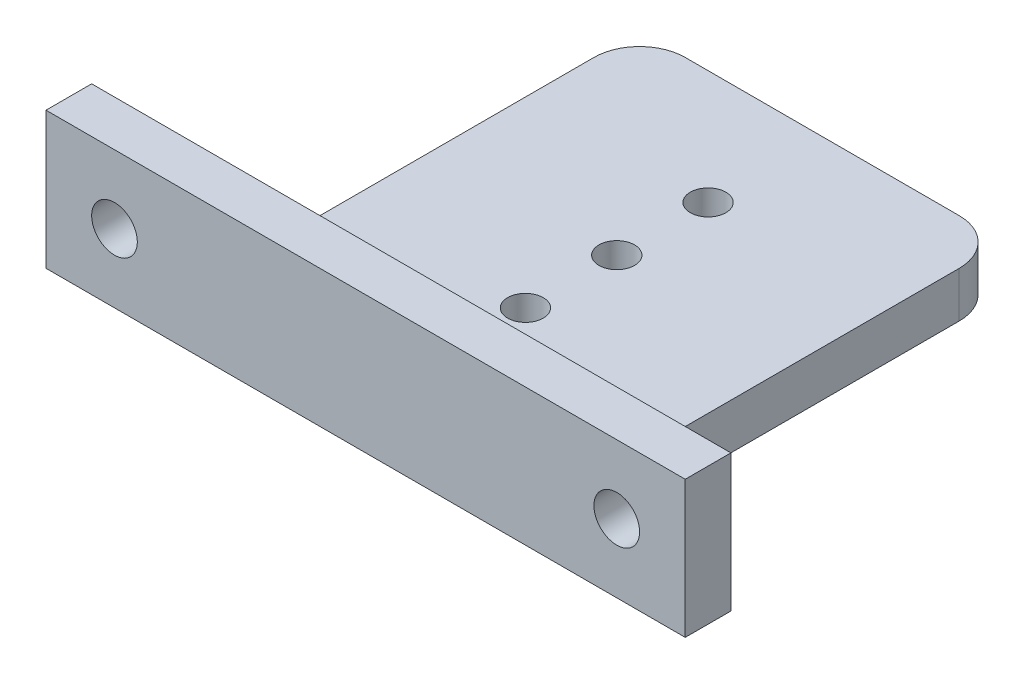
SolidWorks part; units mm, degrees
ref_plane "Front Plane" through (0, 0, 0) normal (0, 0, 1) x (1, 0, 0)
ref_plane "Top Plane" through (0, 0, 0) normal (0, 1, 0) x (1, 0, 0)
ref_plane "Right Plane" through (0, 0, 0) normal (1, 0, 0) x (0, 0, -1)
sketch "Sketch1" plane through (0, 0, 0) normal (0, 1, 0) x (1, 0, 0)
  line L0 (-35, -25) -> (-20, -25)
  line L1 (-20, 25) -> (20, 25)
  line L2 (-20, 25) -> (-20, -20)
  line L4 (20, 25) -> (20, -20)
  line L5 (-20, 25) -> (20, -25) construction
  line L6 (-20, -25) -> (20, 25) construction
  line L7 (-35, -20) -> (-20, -20)
  line L8 (35, -20) -> (35, -25)
  line L9 (-35, -20) -> (-35, -25)
  line L10 (20, -20) -> (35, -20)
  line L11 (20, -25) -> (35, -25)
  line L12 (-20, -25) -> (20, -25)
  point P0 (0, 0)
  dimension "D1" = 50
  dimension "D2" = 40
  dimension "D3" = 15
  dimension "D4" = 15
  dimension "D5" = 5
extrude "Boss-Extrude1" add sketch "Sketch1" along normal blind 5
sketch "Sketch2" plane through (0, 5, 0) normal (0, 1, 0) x (1, 0, 0)
  line L0 (-35, -20) -> (35, -20)
  line L1 (35, -20) -> (35, -25)
  line L2 (35, -25) -> (-35, -25)
  line L3 (-35, -25) -> (-35, -20)
extrude "Boss-Extrude2" add sketch "Sketch2" along normal blind 10
sketch "Sketch3" plane through (0, 5, 0) normal (0, 1, 0) x (1, 0, 0)
  line L0 (-20, 2.5) -> (20, 2.5) construction
  line L1 (-20, 25) -> (-20, -20) construction
  line L2 (20, -20) -> (20, 25) construction
  circle A0 centre (0, 12.5) radius 1.95
  circle A1 centre (0, -7.5) radius 1.95
  circle A3 centre (0, 2.5) radius 1.95
  dimension "D2" = 3.9
  dimension "D3" = 3.9
  dimension "D1" = 10
extrude "Cut-Extrude1" cut sketch "Sketch3" against normal through all
fillet "Fillet1" radius 10 3 edges at (-20, 2.5, 20) (20, 2.5, 20) (0, 5, 20)
sketch "Sketch4" plane through (0, 0, 25) normal (0, 0, 1) x (1, 0, 0)
  line L0 (-35, 7.5) -> (35, 7.5) construction
  line L1 (-35, 15) -> (-35, 0) construction
  line L2 (35, 15) -> (35, 0) construction
  line L3 (0, 15) -> (0, 0) construction
  line L4 (-35, 15) -> (35, 15) construction
  line L5 (-35, 0) -> (35, 0) construction
  circle A0 centre (-27.5, 7.5) radius 2.5
  circle A1 centre (27.5, 7.5) radius 2.5
  dimension "D1" = 5
  dimension "D2" = 7.5
extrude "Cut-Extrude2" cut sketch "Sketch4" against normal through all
sketch "Sketch5" plane through (0, 0, 20) normal (0, 0, -1) x (-1, 0, 0)
  circle A0 centre (27.5, 7.5) radius 5
  circle A1 centre (-27.5, 7.5) radius 5
  dimension "D1" = 10
extrude "Cut-Extrude3" cut sketch "Sketch5" along normal blind 17
fillet "Fillet2" radius 5 2 edges at (-20, 2.5, -25) (20, 2.5, -25)
